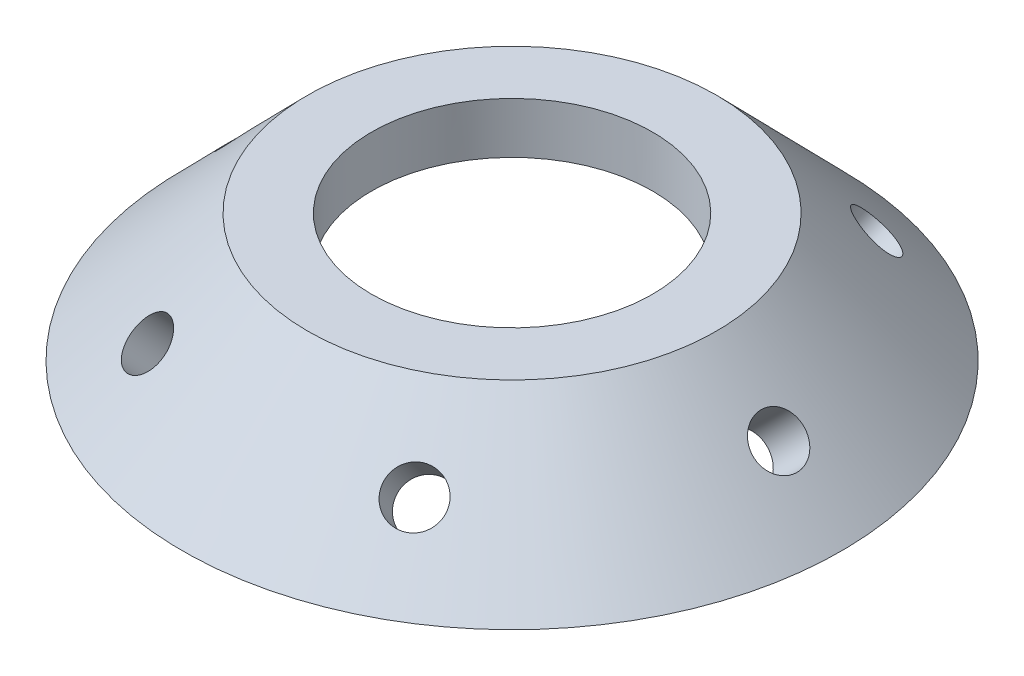
SolidWorks part; units mm, degrees
ref_plane "Front Plane" through (0, 0, 0) normal (0, 0, 1) x (1, 0, 0)
ref_plane "Top Plane" through (0, 0, 0) normal (0, 1, 0) x (1, 0, 0)
ref_plane "Right Plane" through (0, 0, 0) normal (1, 0, 0) x (0, 0, -1)
sketch "Sketch6" plane through (0, 0, 0) normal (0, 0, 1) x (1, 0, 0)
  line L2 (32.2474, -12.5) -> (20, 0)
  line L3 (20, 0) -> (0, 0)
  line L4 (32.2474, -12.5) -> (25.2474, -12.5)
  line L5 (25.2474, -12.5) -> (17.899, -5)
  line L6 (17.899, -5) -> (0, -5)
  line L7 (0, -5) -> (0, 0)
  line L8 (0, -5) -> (0, -12.5) construction
  line L9 (0, -12.5) -> (25.2474, -12.5) construction
  line L10 (32.2474, -12.5) -> (32.2474, -6.25) construction
  line L11 (32.2474, -6.25) -> (26.1237, -6.25) construction
  dimension "D2" = 5
  dimension "D3" = 20
  dimension "D1" = 5
  dimension "D4" = 7
  dimension "D5" = 12.5
  dimension "D6" = 6.25
revolve "Revolve2" add sketch "Sketch6" angle 360 about L7
ref_plane "Plane1" through (10.2041, 9.9979, 0) normal (0.7143, 0.6999, 0) x (0, 0, -1)
sketch "Sketch11" plane through (0, 0, 0) normal (0, 1, 0) x (1, 0, 0)
  line L0 (-20, 0) -> (20, 0) construction
  circle A0 centre (0, 0) radius 13.75
  circle A2 centre (0, 0) radius 20 construction
  dimension "D1" = 27.5
extrude "Cut-Extrude1" cut sketch "Sketch11" against normal through all contours A0
sketch "Sketch24" plane through (10.2041, 9.9979, 0) normal (0.7143, 0.6999, 0) x (0, 0, -1)
  circle A0 centre (0, -22.7471) radius 2.5
  dimension "D1" = 5
extrude "Cut-Extrude2" cut sketch "Sketch24" against normal through all contours A0
pattern_circular "CirPattern10" count 6 over 360 about axis through (0, -5, 0) along (0, -1, 0) of "Cut-Extrude2" reverse direction yes
equation "\"height\"= 3cm"
equation "\"D5@Sketch6\"=\"height\" /2.4"
equation "\"D6@Sketch6\"=\"height\" /4.8"
